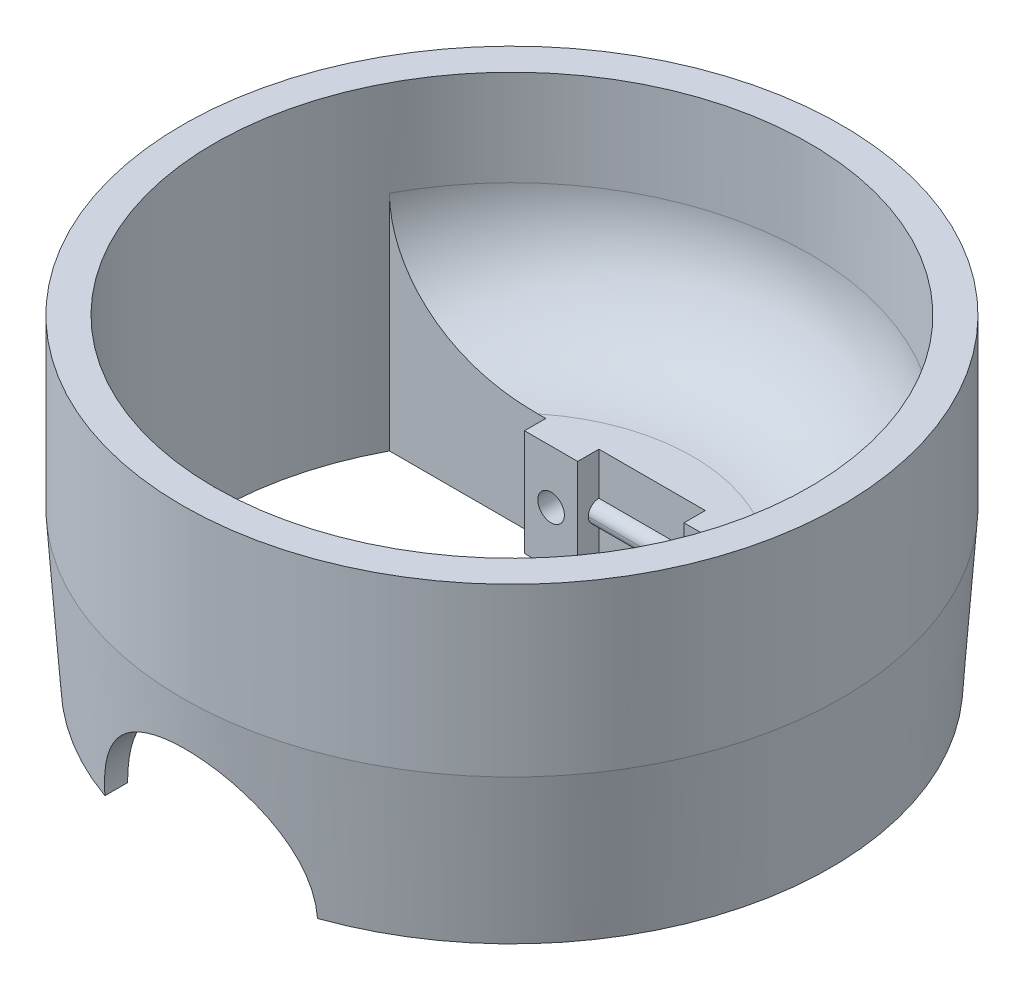
SolidWorks part; units mm, degrees
ref_plane "Front Plane" through (0, 0, 0) normal (0, 0, 1) x (1, 0, 0)
ref_plane "Top Plane" through (0, 0, 0) normal (0, 1, 0) x (1, 0, 0)
ref_plane "Right Plane" through (0, 0, 0) normal (1, 0, 0) x (0, 0, -1)
sketch "Sketch1" plane through (0, 0, 0) normal (0, 1, 0) x (1, 0, 0)
  circle A0 centre (0, 0) radius 31
  circle A1 centre (0, 0) radius 28
  dimension "D1" = 56
  dimension "D2" = 62
extrude "Boss-Extrude1" add sketch "Sketch1" against normal blind 30
sketch "Sketch2" plane through (0, -30, 0) normal (0, -1, 0) x (1, 0, 0)
  line L0 (-24.7019, -13.1839) -> (24.7019, -13.1839)
  arc A0 (-24.7019, -13.1839) -> (24.7019, -13.1839) centre (0, 0) ccw
extrude "Boss-Extrude2" add sketch "Sketch2" against normal blind 10
sketch "Sketch3" plane through (0, 0, -13.1839) normal (0, 0, 1) x (1, 0, 0)
  line L0 (-31, -30) -> (31, -30) construction
  line L1 (-10, -30) -> (10, -30)
  arc A0 (10, -30) -> (-10, -30) centre (0, -30) ccw
extrude "Cut-Extrude1" cut sketch "Sketch3" along normal blind 51
sketch "Sketch4" plane through (0, 0, -13.1839) normal (0, 0, 1) x (1, 0, 0)
  line L0 (-24.7019, -25) -> (24.7019, -25) construction
  line L1 (-24.7019, -20) -> (-24.7019, -30) construction
  line L2 (24.7019, -20) -> (24.7019, -30) construction
  line L3 (0, -20) -> (0, -30) construction
  line L4 (24.7019, -20) -> (-24.7019, -20) construction
  line L5 (24.7019, -30) -> (-24.7019, -30) construction
  line L6 (-5, -20) -> (-5, -30)
  line L7 (5, -20) -> (5, -30)
  line L8 (-10, -20) -> (-10, -30)
  line L9 (10, -20) -> (10, -30)
  line L10 (-10, -20) -> (-5, -20)
  line L11 (-10, -30) -> (-5, -30)
  line L12 (5, -20) -> (10, -20)
  line L13 (5, -30) -> (10, -30)
  line L14 (-7.5, -20) -> (-7.5, -30) construction
  line L15 (7.5, -20) -> (7.5, -30) construction
  line L16 (-5, -24) -> (-5, -26)
  line L17 (-5, -26) -> (5, -26)
  line L18 (-5, -24) -> (5, -24)
  line L19 (5, -24) -> (5, -26)
  circle A0 centre (-7.5, -25) radius 1.25
  circle A1 centre (7.5, -25) radius 1.25
  dimension "D5" = 2.5
  dimension "D6" = 2.5
  dimension "D1" = 5
  dimension "D2" = 5
  dimension "D3" = 5
  dimension "D4" = 5
extrude "Boss-Extrude3" add sketch "Sketch4" along normal blind 2 contours L16 L8 L19 L6 A0 | L9 L16 L7 L19 A1 region at (-5.1118, -22, -13.1839) region at (5.1118, -22, -13.1839)
extrude "Boss-Extrude4" add sketch "Sketch4<3>" along normal blind 1 contours L18 L6 L17 L7 region at (0, -25, -13.1839)
sketch "Sketch4<3>" plane through (0, 0, -13.1839) normal (0, 0, 1) x (1, 0, 0) same geometry as "Sketch4"
extrude "Cut-Extrude2" cut sketch "Sketch4<4>" against normal blind 6 contours A0 | A1 region at (-7.5, -25, -13.1839) region at (7.5, -25, -13.1839)
sketch "Sketch4<4>" plane through (0, 0, -13.1839) normal (0, 0, 1) x (1, 0, 0) same geometry as "Sketch4"
fillet "Fillet1" radius 1 2 edges at (0, -24, -12.1839) (0, -26, -12.1839)
chamfer "Chamfer1" distance 1 angle 86 1 edges at (0, -30, -31) first distance on face at (0, -30, -4.7539)
fillet "Fillet3" radius 11 1 edges at (0, -20, -28)
